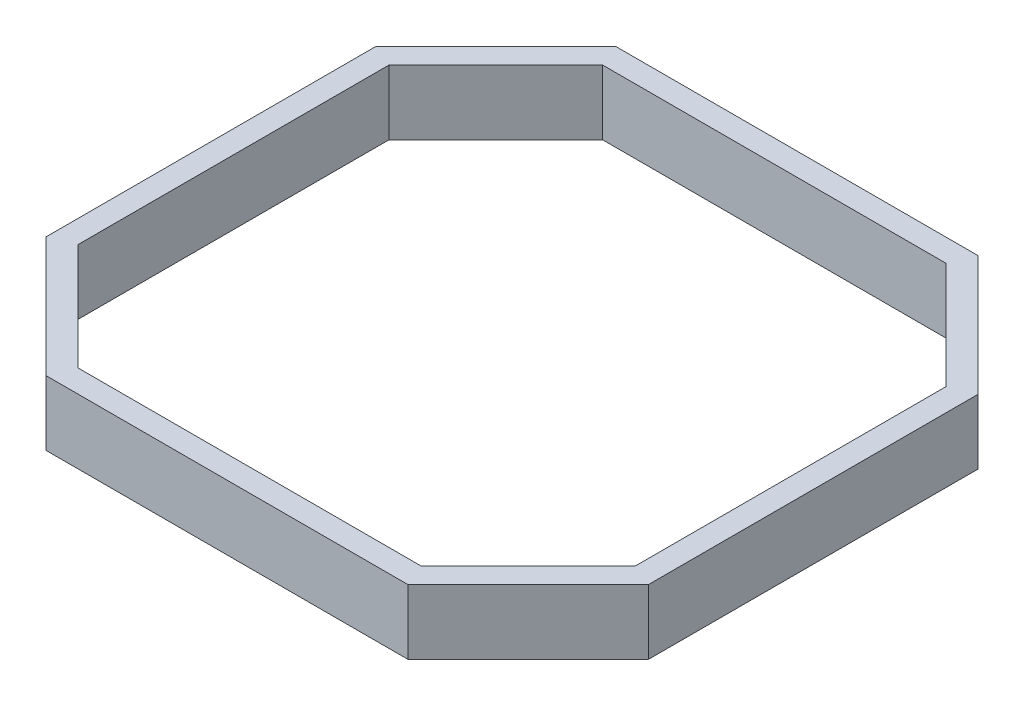
SolidWorks part; units mm, degrees
material "Copper"
ref_plane "Front Plane" through (0, 0, 0) normal (0, 0, 1) x (1, 0, 0)
ref_plane "Top Plane" through (0, 0, 0) normal (0, 1, 0) x (1, 0, 0)
ref_plane "Right Plane" through (0, 0, 0) normal (1, 0, 0) x (0, 0, -1)
sketch "Sketch1" plane through (0, 0, 0) normal (0, 1, 0) x (1, 0, 0)
  line L0 (-43, 24) -> (-26.5, 40.5)
  line L1 (-26.5, -40.5) -> (26.5, -40.5)
  line L2 (-43, -24) -> (-43, 24)
  line L3 (-26.5, 40.5) -> (26.5, 40.5)
  line L4 (43, -24) -> (43, 24)
  line L5 (0, 0) -> (0, -40.5) construction
  line L6 (0, 0) -> (-43, 0) construction
  line L7 (-43, -24) -> (-26.5, -40.5)
  line L8 (26.5, -40.5) -> (43, -24)
  line L9 (26.5, 40.5) -> (43, 24)
  line L10 (0, 0) -> (0, 40.5) construction
  line L11 (0, 0) -> (43, 0) construction
  line L12 (-46.5, 25.4497) -> (-27.9497, 44)
  line L13 (-27.9497, 44) -> (27.9497, 44)
  line L14 (27.9497, 44) -> (46.5, 25.4497)
  line L15 (46.5, -25.4497) -> (46.5, 25.4497)
  line L16 (27.9497, -44) -> (46.5, -25.4497)
  line L17 (-27.9497, -44) -> (27.9497, -44)
  line L18 (-46.5, -25.4497) -> (-27.9497, -44)
  line L19 (-46.5, -25.4497) -> (-46.5, 25.4497)
  point P0 (0, 0)
  dimension "D1" = 86
  dimension "D2" = 81
  dimension "D3" = 48
  dimension "D4" = 53
  dimension "D5" = 3.5
extrude "Boss-Extrude1" add sketch "Sketch1" along normal blind 10
